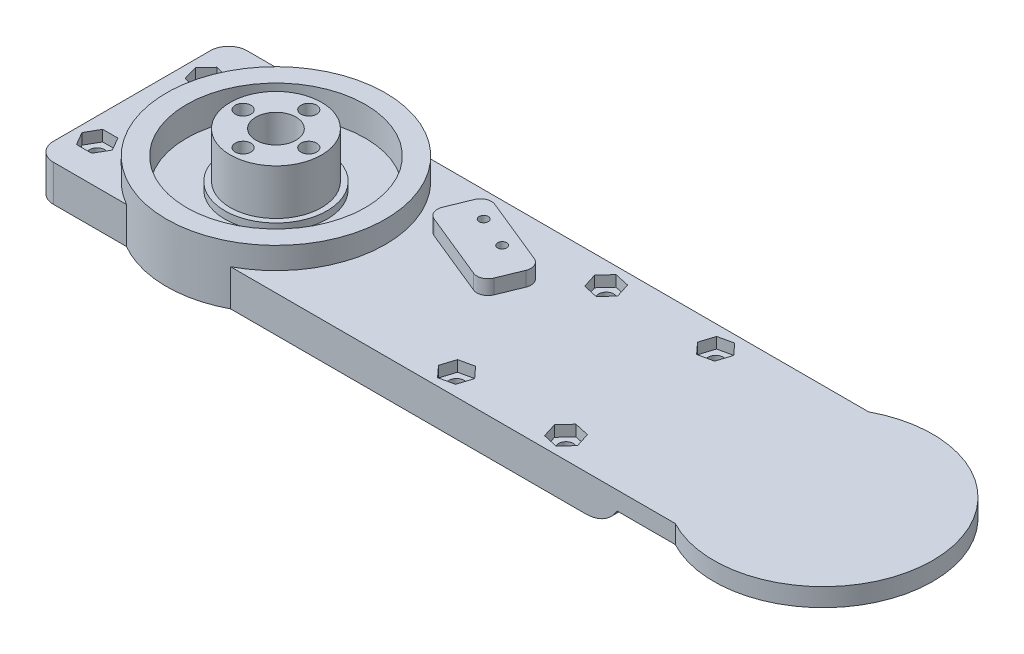
SolidWorks part; units mm, degrees
ref_plane "Front Plane" through (0, 0, 0) normal (0, 0, 1) x (1, 0, 0)
ref_plane "Top Plane" through (0, 0, 0) normal (0, 1, 0) x (1, 0, 0)
ref_plane "Right Plane" through (0, 0, 0) normal (1, 0, 0) x (0, 0, -1)
sketch "Sketch1" plane through (0, 0, 0) normal (0, 1, 0) x (1, 0, 0)
  line L0 (-75, 0) -> (75, 0) construction
  line L1 (-60.9376, 26.5) -> (60.9376, 26.5)
  line L3 (-60.9376, -26.5) -> (60.9376, -26.5)
  arc A0 (-60.9376, 26.5) -> (-60.9376, -26.5) centre (-75, 0) ccw
  arc A1 (60.9376, -26.5) -> (60.9376, 26.5) centre (75, 0) ccw
  point P0 (0, 0)
  dimension "D3" = 60
  dimension "D4" = 60
  dimension "D1" = 150
extrude "Boss-Extrude1" add sketch "Sketch1" along normal blind 10
sketch "Sketch2" plane through (0, 10, 0) normal (0, 1, 0) x (1, 0, 0)
  circle A0 centre (-75, 0) radius 30
  arc A1 (-60.9376, 26.5) -> (-60.9376, -26.5) centre (-75, 0) ccw construction
  dimension "D1" = 60
extrude "Boss-Extrude2" add sketch "Sketch2" along normal blind 6
sketch "Sketch3" plane through (0, 16, 0) normal (0, 1, 0) x (1, 0, 0)
  circle A0 centre (-75, 0) radius 24.5
  dimension "D1" = 49
extrude "Cut-Extrude1" cut sketch "Sketch3" against normal blind 8
sketch "Sketch4" plane through (0, 8, 0) normal (0, 1, 0) x (1, 0, 0)
  circle A1 centre (-75, 0) radius 14
  dimension "D1" = 28
extrude "Boss-Extrude3" add sketch "Sketch4" along normal blind 2
sketch "Sketch5" plane through (0, 10, 0) normal (0, 1, 0) x (1, 0, 0)
  circle A0 centre (-75, 0) radius 12.5
  dimension "D1" = 25
extrude "Boss-Extrude4" add sketch "Sketch5" along normal blind 12.5
sketch "Sketch6" plane through (0, 22.5, 0) normal (0, 1, 0) x (1, 0, 0)
  circle A0 centre (-75, 0) radius 9 construction
  circle A1 centre (-75, 9) radius 2.15
  circle A2 centre (-66, 0) radius 2.15
  circle A3 centre (-75, -9) radius 2.15
  circle A4 centre (-84, 0) radius 2.15
  dimension "D1" = 18
  dimension "D2" = 4.3
extrude "Cut-Extrude2" cut sketch "Sketch6" against normal through all
ref_axis "Axis1" through (-75, 16, 0) along (0, -1, 0)
sketch "Sketch9" plane through (0, 0, 0) normal (0, -1, 0) x (1, 0, 0)
  line L1 (-86.3413, 25.9659) -> (-115, 25.9659)
  line L2 (-86.3413, 25.9659) -> (-86.3413, -27.0341)
  line L3 (-86.3413, -27.0341) -> (-115, -27.0341)
  line L4 (-115, 25.9659) -> (-115, -27.0341)
  line L5 (-86.3413, 25.9659) -> (-115, -27.0341) construction
  line L6 (-86.3413, -27.0341) -> (-115, 25.9659) construction
  point P0 (-100.6707, -0.5341)
  dimension "D1" = 53
  dimension "D2" = 40
extrude "Boss-Extrude5" add sketch "Sketch9" against normal blind 10
fillet "Fillet1" radius 5 2 edges at (-115, 5, 25.9659) (-115, 5, -27.0341)
sketch "Sketch12" plane through (0, 10, 0) normal (0, 1, 0) x (1, 0, 0)
  line L0 (-43.1667, 9.8756) -> (-38.3507, 21.672)
  line L1 (-38.3507, 21.672) -> (-14.4886, 11.9302)
  line L2 (-14.4886, 11.9302) -> (-19.3046, 0.1338)
  line L3 (-19.3046, 0.1338) -> (-43.1667, 9.8756)
extrude "Boss-Extrude6" add sketch "Sketch12" along normal blind 4
sketch "Sketch14" plane through (0, 14, 0) normal (0, 1, 0) x (1, 0, 0)
  circle A0 centre (-33.5642, 15.4944) radius 1.25
  circle A1 centre (-24.8102, 11.8042) radius 1.25
extrude "Cut-Extrude7" cut sketch "Sketch14" against normal up to next
fillet "Fillet2" radius 3 4 edges at (-19.3046, 12, -0.1338) (-14.4886, 12, -11.9302) (-43.1667, 12, -9.8756) (-38.3507, 12, -21.672)
sketch "Sketch16" plane through (0, 22.5, 0) normal (0, 1, 0) x (1, 0, 0)
  circle A0 centre (-75, 0) radius 5.5
  dimension "D1" = 11
extrude "Cut-Extrude11" cut sketch "Sketch16" against normal up to next
sketch "Sketch17" plane through (0, 8, 0) normal (0, 1, 0) x (1, 0, 0)
  circle A0 centre (-75, 0) radius 24.5
  circle A1 centre (-75, 0) radius 14
extrude "Cut-Extrude13" cut sketch "Sketch17" along normal blind 10
sketch "Sketch18" plane through (0, 0, 0) normal (0, -1, 0) x (1, 0, 0)
  line L0 (-5, -20.5) -> (25, -20.5) construction
  line L1 (60.9376, -26.5) -> (-60.9376, -26.5) construction
  circle A0 centre (-5, -20.5) radius 2.05
  circle A1 centre (25, -20.5) radius 2.05
  circle A2 centre (75, 0) radius 6.4986 construction
  dimension "D2" = 4.1
  dimension "D3" = 4.1
  dimension "D1" = 30
  dimension "D4" = 50
  dimension "D5" = 6
extrude "Cut-Extrude14" cut sketch "Sketch18" against normal up to next
sketch "Sketch19" plane through (0, 10, 0) normal (0, 1, 0) x (1, 0, 0)
  line L1 (-3.75, 16.5355) -> (-0.9416, 19.6002)
  line L2 (-0.9416, 19.6002) -> (-2.1916, 23.5648)
  line L3 (-2.1916, 23.5648) -> (-6.25, 24.4645)
  line L4 (-6.25, 24.4645) -> (-9.0584, 21.3998)
  line L5 (-9.0584, 21.3998) -> (-7.8084, 17.4352)
  line L6 (-7.8084, 17.4352) -> (-3.75, 16.5355)
  line L7 (23.75, 16.5355) -> (27.8084, 17.4352)
  line L8 (27.8084, 17.4352) -> (29.0584, 21.3998)
  line L9 (29.0584, 21.3998) -> (26.25, 24.4645)
  line L10 (26.25, 24.4645) -> (22.1916, 23.5648)
  line L11 (22.1916, 23.5648) -> (20.9416, 19.6002)
  line L12 (20.9416, 19.6002) -> (23.75, 16.5355)
  circle A0 centre (-5, 20.5) radius 3.6 construction
  circle A1 centre (25, 20.5) radius 3.6 construction
  dimension "D1" = 7.2
  dimension "D2" = 7.2
extrude "Cut-Extrude15" cut sketch "Sketch19" against normal blind 3
mirror "Mirror1" about plane through (0, 0, 0) normal (0, 0, 1) of "Cut-Extrude14", "Cut-Extrude15"
sketch "Sketch20" plane through (0, 10, 0) normal (0, 1, 0) x (1, 0, 0)
  line L0 (-109, 15) -> (-109, -15) construction
  line L1 (-115, -20.9659) -> (-115, 22.0341) construction
  circle A0 centre (-109, 15) radius 2.05
  circle A1 centre (-109, -15) radius 2.05
  point P6 (-109, 0)
  dimension "D1" = 4.1
  dimension "D2" = 4.1
  dimension "D3" = 30
  dimension "D4" = 6
extrude "Cut-Extrude16" cut sketch "Sketch20" against normal up to next
sketch "Sketch21" plane through (0, 10, 0) normal (0, 1, 0) x (1, 0, 0)
  line L1 (-107.8397, 11.0083) -> (-104.9629, 14.009)
  line L2 (-104.9629, 14.009) -> (-106.1232, 18.0007)
  line L3 (-106.1232, 18.0007) -> (-110.1603, 18.9917)
  line L4 (-110.1603, 18.9917) -> (-113.0371, 15.991)
  line L5 (-113.0371, 15.991) -> (-111.8768, 11.9993)
  line L6 (-111.8768, 11.9993) -> (-107.8397, 11.0083)
  line L7 (-113.1569, -15) -> (-111.0785, -18.6)
  line L8 (-111.0785, -18.6) -> (-106.9215, -18.6)
  line L9 (-106.9215, -18.6) -> (-104.8431, -15)
  line L10 (-104.8431, -15) -> (-106.9215, -11.4)
  line L11 (-106.9215, -11.4) -> (-111.0785, -11.4)
  line L12 (-111.0785, -11.4) -> (-113.1569, -15)
  circle A0 centre (-109, 15) radius 3.6 construction
  circle A1 centre (-109, -15) radius 3.6 construction
  dimension "D1" = 7.2
  dimension "D2" = 7.2
extrude "Cut-Extrude17" cut sketch "Sketch21" against normal blind 3
sketch "Sketch22" plane through (0, 0, 0) normal (0, -1, 0) x (1, 0, 0)
  line L1 (45, 43.9771) -> (105, 43.9771)
  line L2 (45, 43.9771) -> (45, -43.9771)
  line L3 (45, -43.9771) -> (105, -43.9771)
  line L4 (105, 43.9771) -> (105, -43.9771)
  line L5 (45, 43.9771) -> (105, -43.9771) construction
  line L6 (45, -43.9771) -> (105, 43.9771) construction
  point P0 (75, 0)
extrude "Cut-Extrude18" cut sketch "Sketch22" against normal blind 5
fillet "Fillet3" radius 10 1 edges at (45, 0, 0)
sketch "Sketch23" plane through (0, 5, 0) normal (0, -1, 0) x (1, 0, 0)
  line L1 (47.6608, 10.9308) -> (59.3506, 10.9308)
  line L2 (47.6608, 10.9308) -> (47.6608, 6.9308)
  line L3 (47.6608, 6.9308) -> (59.3506, 6.9308)
  line L4 (59.3506, 10.9308) -> (59.3506, 6.9308)
  dimension "D1" = 4
extrude "Boss-Extrude7" add sketch "Sketch23" along normal blind 5
sketch "Sketch24" plane through (0, 0, 10.9308) normal (0, 0, 1) x (1, 0, 0)
  line L0 (47.6608, 0) -> (47.6608, 5) construction
  line L1 (47.6608, 2) -> (59.3506, 2)
  line L2 (47.6608, 2) -> (47.6608, 0)
  line L3 (47.6608, 0) -> (59.3506, 0)
  line L4 (59.3506, 2) -> (59.3506, 0)
  line L5 (59.3506, 0) -> (47.6608, 0) construction
  line L6 (59.3506, 0) -> (59.3506, 5) construction
  dimension "D1" = 2
extrude "Boss-Extrude8" add sketch "Sketch24" along normal blind 8
sketch "Sketch25" plane through (59.3506, 0, 0) normal (1, 0, 0) x (0, 0, -1)
  line L0 (-6.9308, 0) -> (-1.9308, 5)
  line L1 (-26.5, 5) -> (26.5, 5) construction
  dimension "D1" = 45
rib "Rib1" sketch "Sketch25" sketch "Sketch25" thickness 11.5 extrusion direction parallel to sketch draft on no parameters "D1"=11.5
